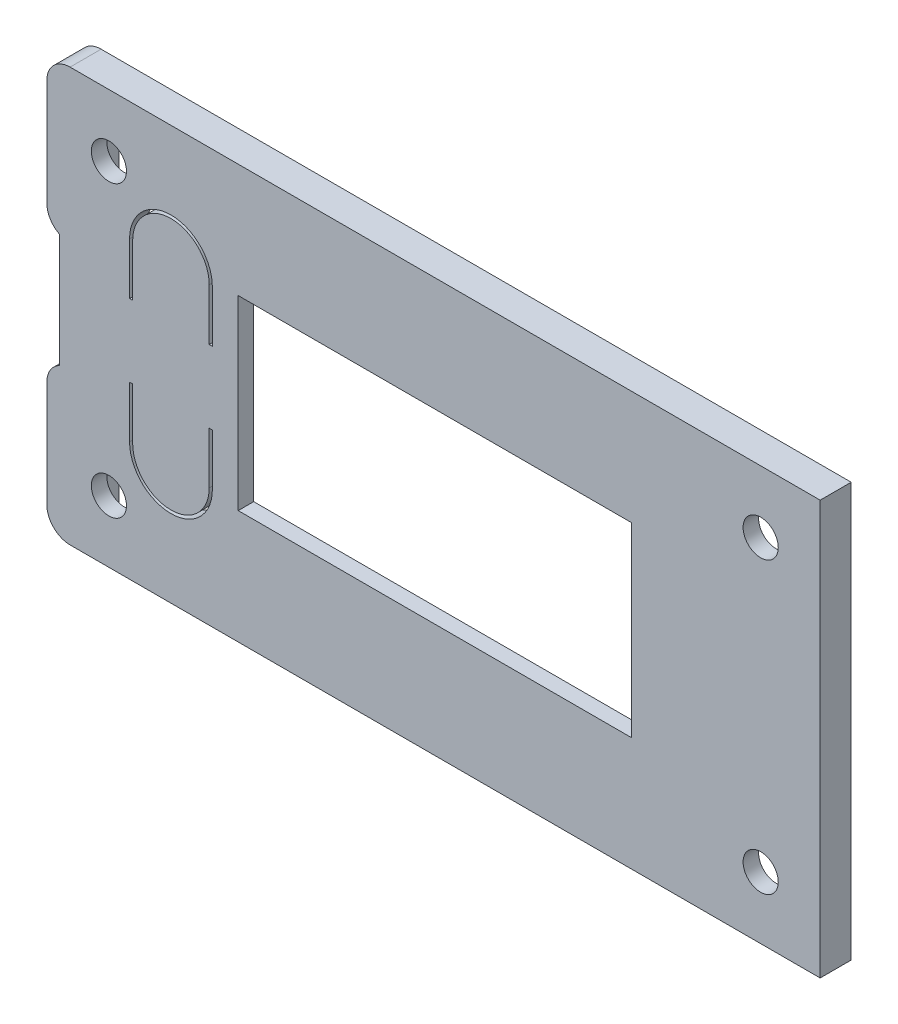
SolidWorks part; units mm, degrees
ref_plane "Front Plane" through (0, 0, 0) normal (0, 0, 1) x (1, 0, 0)
ref_plane "Top Plane" through (0, 0, 0) normal (0, 1, 0) x (1, 0, 0)
ref_plane "Right Plane" through (0, 0, 0) normal (1, 0, 0) x (0, 0, -1)
sketch "Sketch1" plane through (0, 0, 0) normal (0, 0, 1) x (1, 0, 0)
  line L1 (0, 0) -> (74.75, 0)
  line L2 (0, 0) -> (0, 40)
  line L3 (0, 40) -> (74.75, 40)
  line L4 (74.75, 0) -> (74.75, 40)
  dimension "D1" = 40
  dimension "D2" = 74.75
extrude "Boss-Extrude1" add sketch "Sketch1" along normal blind 3
sketch "Sketch2" plane through (0, 0, 3) normal (0, 0, 1) x (1, 0, 0)
  line L0 (0, 40) -> (0, 0) construction
  line L1 (0, 25.25) -> (2.25, 25.25)
  line L2 (0, 25.25) -> (0, 14.75)
  line L3 (0, 14.75) -> (2.25, 14.75)
  line L4 (2.25, 25.25) -> (2.25, 14.75)
  line L5 (0, 20) -> (2.25, 20) construction
  dimension "D1" = 2.25
  dimension "D2" = 10.5
extrude "Cut-Extrude1" cut sketch "Sketch2" against normal through all
fillet "Fillet2" radius 2.25 2 edges at (0, 14.75, 1.5) (0, 25.25, 1.5)
fillet "Fillet1" radius 2.25 2 edges at (0, 0, 1.5) (0, 40, 1.5)
sketch "Sketch6" plane through (0, 0, 3) normal (0, 0, 1) x (1, 0, 0)
  line L2 (1.25, 25.4844) -> (1.25, 14.5156)
  line L4 (2.25, 25.25) -> (2.25, 14.75)
  arc A0 (0, 27.5) -> (2.25, 25.25) centre (2.25, 27.5) ccw construction
  arc A1 (2.25, 14.75) -> (0, 12.5) centre (2.25, 12.5) ccw construction
  arc A2 (1.25, 25.4844) -> (2.25, 25.25) centre (2.25, 27.5) ccw
  arc A3 (1.25, 14.5156) -> (2.25, 14.75) centre (2.25, 12.5) cw
  dimension "D1" = 1
  dimension "D2" = 2.25
  dimension "D3" = 2.25
extrude "Boss-Extrude4" add sketch "Sketch6" against normal blind 3.7
sketch "Sketch7" plane through (0, 0, 0) normal (0, 0, -1) x (-1, 0, 0)
  line L0 (-2.25, 0) -> (-74.75, 0) construction
  line L1 (-74.75, 40) -> (-2.25, 40) construction
  line L2 (0, 37.75) -> (0, 27.5) construction
  line L4 (-4, 37.75) -> (-72.5, 37.75)
  line L8 (-4, 37.75) -> (-4, 2.25)
  line L9 (-4, 2.25) -> (-72.5, 2.25)
  line L10 (-72.5, 37.75) -> (-72.5, 2.25)
  line L11 (-74.75, 0) -> (-74.75, 40) construction
  point P12 (0, 32.625)
  dimension "D1" = 2.25
  dimension "D2" = 2.25
  dimension "D3" = 2.25
  dimension "D4" = 4
extrude "oled-recess" cut sketch "Sketch7" against normal blind 1.5
sketch "Sketch9" plane through (0, 0, 3) normal (0, 0, 1) x (1, 0, 0)
  line L0 (0, 34) -> (74.75, 34) construction
  line L1 (0, 37.75) -> (0, 27.5) construction
  line L2 (74.75, 0) -> (74.75, 40) construction
  line L3 (0, 6) -> (74.75, 6) construction
  line L4 (0, 12.5) -> (0, 2.25) construction
  line L5 (6, 40) -> (6, 0) construction
  line L6 (74.75, 40) -> (2.25, 40) construction
  line L7 (2.25, 0) -> (74.75, 0) construction
  line L8 (69, 40) -> (69, 0) construction
  line L9 (12, 34) -> (12, 6) construction
  line L10 (18.5, 29) -> (56.5, 29)
  line L11 (18.5, 29) -> (18.5, 11)
  line L12 (18.5, 11) -> (56.5, 11)
  line L13 (56.5, 29) -> (56.5, 11)
  line L14 (8, 28.5) -> (8, 23.5)
  line L15 (16, 28.5) -> (16, 23.5)
  line L16 (15.7, 28.5) -> (15.7, 23.5)
  line L17 (8.3, 28.5) -> (8.3, 23.5)
  line L18 (8, 23.5) -> (8.3, 23.5)
  line L19 (15.7, 23.5) -> (16, 23.5)
  line L20 (16, 23.5) -> (8, 23.5) construction
  line L21 (1.25, 25.4844) -> (1.25, 14.5156) construction
  line L22 (1.25, 20) -> (17.0967, 20) construction
  line L23 (15.7, 16.5) -> (16, 16.5)
  line L24 (8, 16.5) -> (8.3, 16.5)
  line L25 (8.3, 11.5) -> (8.3, 16.5)
  line L26 (15.7, 11.5) -> (15.7, 16.5)
  line L27 (16, 11.5) -> (16, 16.5)
  line L28 (8, 11.5) -> (8, 16.5)
  circle A0 centre (6, 34) radius 1.7
  circle A1 centre (69, 34) radius 1.7
  circle A2 centre (6, 6) radius 1.7
  circle A3 centre (69, 6) radius 1.7
  arc A4 (8, 28.5) -> (16, 28.5) centre (12, 28.5) cw
  arc A5 (8.3, 28.5) -> (15.7, 28.5) centre (12, 28.5) cw
  arc A6 (8.3, 11.5) -> (15.7, 11.5) centre (12, 11.5) ccw
  arc A7 (8, 11.5) -> (16, 11.5) centre (12, 11.5) ccw
  point P18 (0, 32.625)
  point P19 (69, 20)
  point P46 (1.25, 20)
  dimension "D5" = 3.4
  dimension "D6" = 3.4
  dimension "D7" = 3.4
  dimension "D8" = 3.4
  dimension "D16" = 4
  dimension "D1" = 6
  dimension "D2" = 5.75
  dimension "D3" = 14
  dimension "D4" = 14
  dimension "D9" = 5
  dimension "D10" = 5
  dimension "D11" = 12.5
  dimension "D12" = 12.5
  dimension "D13" = 6
  dimension "D14" = 5
  dimension "D17" = 8.5
  dimension "D15" = 0.3
extrude "Cut-Extrude5" cut sketch "Sketch9" against normal through all
